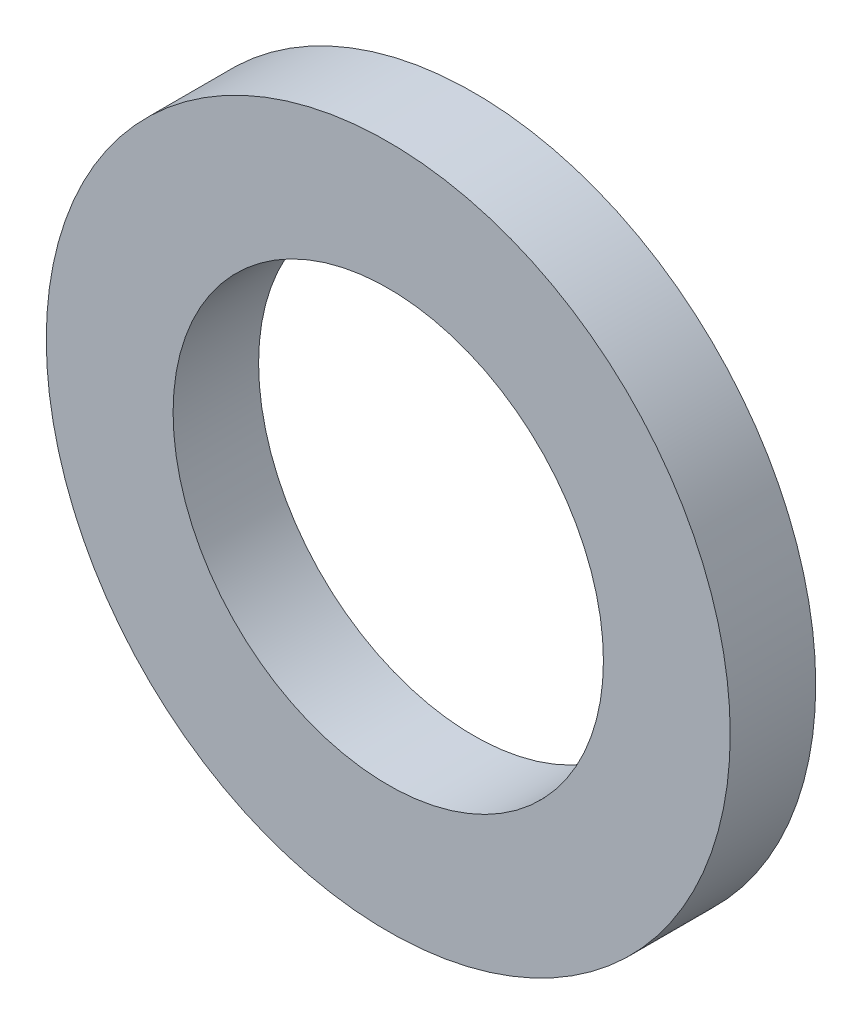
SolidWorks part; units mm, degrees
ref_plane "Ebene vorne (XY)" through (0, 0, 0) normal (0, 0, 1) x (1, 0, 0)
ref_plane "Ebene oben  (XZ)" through (0, 0, 0) normal (0, 1, 0) x (1, 0, 0)
ref_plane "Ebene rechts  (YZ)" through (0, 0, 0) normal (1, 0, 0) x (0, 0, -1)
ref_axis "x-Achse" through (-13.2, 0, 0) along (1, 0, 0)
ref_axis "y-Achse" through (0, 13.2, 0) along (0, -1, 0)
ref_axis "z-Achse" through (0, 0, -0.15) along (0, 0, 1)
sketch "Profile_Laser_profile_3mm" plane through (0, 0, 0) normal (0, 0, 1) x (1, 0, 0)
  circle A0 centre (0, 0) radius 12
  circle A1 centre (0, 0) radius 7.55
extrude "Laser_profile_3mm" add sketch "Profile_Laser_profile_3mm" along normal blind 3
